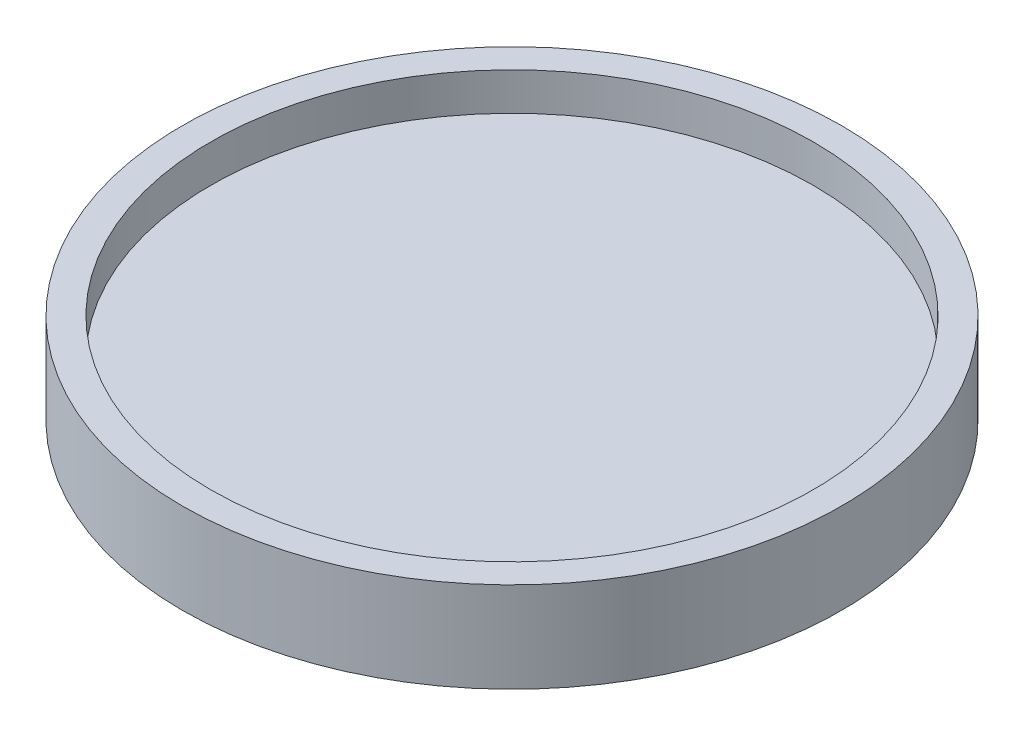
SolidWorks part; units mm, degrees
ref_plane "Front Plane" through (0, 0, 0) normal (0, 0, 1) x (1, 0, 0)
ref_plane "Top Plane" through (0, 0, 0) normal (0, 1, 0) x (1, 0, 0)
ref_plane "Right Plane" through (0, 0, 0) normal (1, 0, 0) x (0, 0, -1)
sketch "Sketch2" plane through (0, 0, 0) normal (0, 1, 0) x (1, 0, 0)
  circle A0 centre (0, 0) radius 11.1125
extrude "Boss-Extrude1" add sketch "Sketch2" along normal blind 3.048
sketch "Sketch3" plane through (0, 3.048, 0) normal (0, 1, 0) x (1, 0, 0)
  circle A0 centre (0, 0) radius 10.16
  dimension "D1" = 20.32
extrude "Cut-Extrude1" cut sketch "Sketch3" against normal blind 1.27
sketch "Sketch4" plane through (0, 0, 0) normal (0, -1, 0) x (-1, 0, 0)
  circle A0 centre (0, 0) radius 3.81
extrude "Cut-Extrude2" cut sketch "Sketch4" against normal blind 1.27 contours A0
fillet "Fillet1" radius 15.08 1 edges at (0, 0, -3.81)
